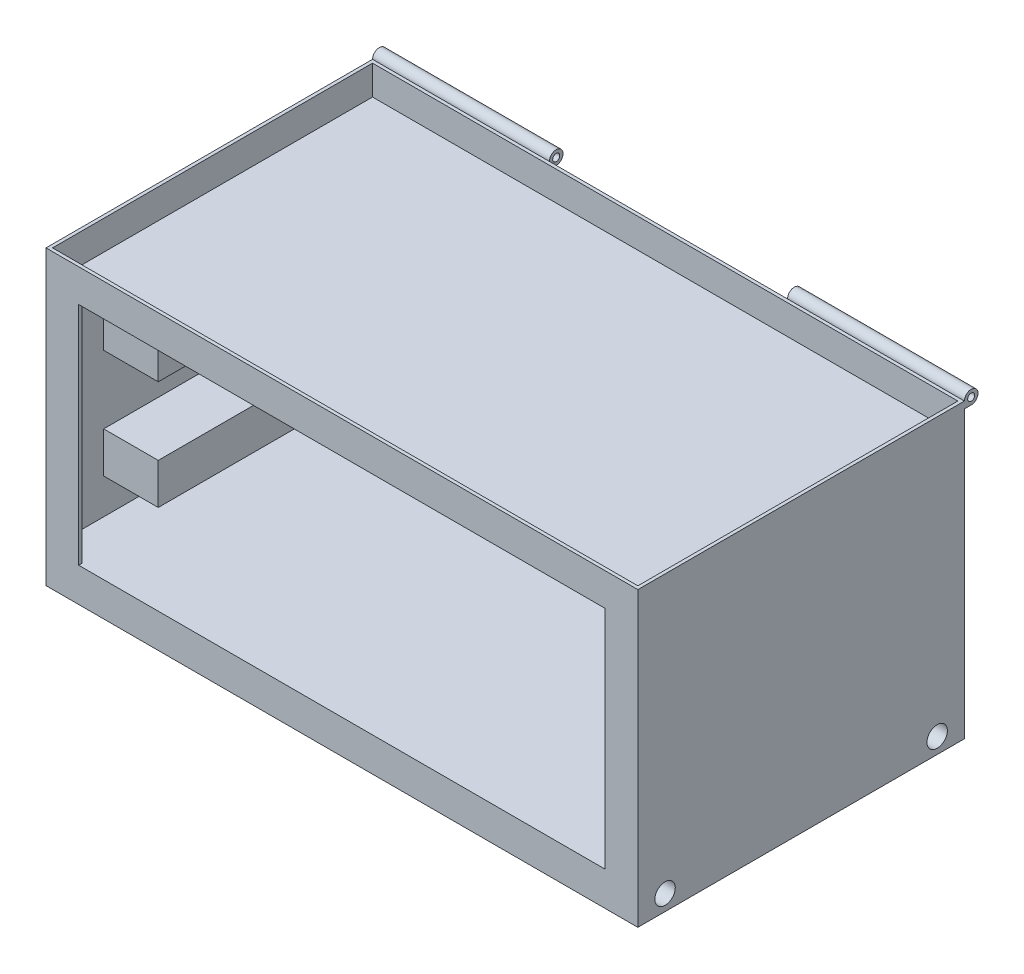
SolidWorks part; units mm, degrees
note: The reader was unsure of these and kept them because the rebuilt part matched: shared geometry of "Sketch1<13>", "Sketch1<14>", "Sketch1<15>".
material "AISI 4130 Steel, normalized at 870C"
ref_plane "Front Plane" through (0, 0, 0) normal (0, 0, 1) x (1, 0, 0)
ref_plane "Top Plane" through (0, 0, 0) normal (0, 1, 0) x (1, 0, 0)
ref_plane "Right Plane" through (0, 0, 0) normal (1, 0, 0) x (0, 0, -1)
sketch "Sketch1" plane through (0, 0, 0) normal (0, 1, 0) x (1, 0, 0)
  line L0 (0, 0) -> (-1.524, 0) construction
  line L9 (0, 0) -> (273.177, 0)
  line L10 (0, 0) -> (0, 149.352)
  line L11 (0, 149.352) -> (273.177, 149.352)
  line L12 (273.177, 0) -> (273.177, 149.352)
  line L13 (-1.524, -1.524) -> (274.701, -1.524)
  line L14 (-1.524, -1.524) -> (-1.524, 150.876)
  line L15 (-1.524, 150.876) -> (274.701, 150.876)
  line L16 (274.701, -1.524) -> (274.701, 150.876)
  line L17 (0, 149.352) -> (0, 150.876) construction
  line L18 (273.177, 149.352) -> (274.701, 149.352) construction
  line L19 (273.177, 0) -> (273.177, -1.524) construction
  line L20 (13.716, 0) -> (13.716, -1.524)
  line L21 (136.5885, 150.876) -> (136.5885, -1.524) construction
  line L22 (259.461, 0) -> (259.461, -1.524)
  dimension "D1" = 1.524
  dimension "D2" = 276.225
  dimension "D3" = 152.4
  dimension "D4" = 15.24
extrude "Bulk-Extrude" add sketch "Sketch1" against normal blind 136.525 contours L14 L13 L16 L15
extrude "Inner Shell-Cut" cut sketch "Sketch1<13>" against normal offset from surface (120.65 mm away) 15.875 contours L9 L12 L11 L10 | L22 L9 L20 L13 up to face at (136.5885, -136.525, -74.676)
sketch "Sketch1<13>" plane through (0, 0, 0) normal (0, 1, 0) x (1, 0, 0) same geometry as "Sketch1"
extrude "Top Wall-Extrude" add sketch "Sketch1<14>" against normal blind 15.24 contours L22 L9 L20 L13
sketch "Sketch1<14>" plane through (0, 0, 0) normal (0, 1, 0) x (1, 0, 0) same geometry as "Sketch1"
extrude "Top Floor-Extrude" add sketch "Sketch1<15>" along normal blind 1.524 from surface at -15.24 contours L9 L12 L11 L10 starting at face at (136.5885, -15.24, 0.762)
sketch "Sketch1<15>" plane through (0, 0, 0) normal (0, 1, 0) x (1, 0, 0) same geometry as "Sketch1"
ref_plane "Mid Plane" through (136.5885, 0, 0) normal (1, 0, 0) x (0, 0, -1)
sketch "Sketch5" plane through (274.701, 0, 0) normal (1, 0, 0) x (0, 0, -1)
  line L0 (150.876, 0) -> (154.051, 0)
  line L2 (154.051, -3.175) -> (150.876, -3.175)
  line L3 (150.876, -136.525) -> (150.876, 0) construction
  circle A0 centre (154.051, 0) radius 3.175
  circle A1 centre (154.051, 0) radius 1.651
  dimension "D1" = 1.524
  dimension "D2" = 6.35
extrude "Hinge-Extrude" add sketch "Sketch5" against normal blind 82.55
mirror "Mirror1" about plane through (136.5885, 0, 0) normal (1, 0, 0) of "Hinge-Extrude"
sketch "Sketch7" plane through (0, 0, -149.352) normal (0, 0, 1) x (1, 0, 0)
  line L0 (273.177, -120.65) -> (273.177, -15.24) construction
  line L1 (0, -34.29) -> (25.4635, -34.29)
  line L2 (0, -34.29) -> (0, -53.34)
  line L3 (0, -53.34) -> (25.4635, -53.34)
  line L4 (25.4635, -34.29) -> (25.4635, -53.34)
  line L5 (273.177, -34.29) -> (247.7135, -34.29)
  line L6 (273.177, -34.29) -> (273.177, -53.34)
  line L7 (273.177, -53.34) -> (247.7135, -53.34)
  line L8 (247.7135, -34.29) -> (247.7135, -53.34)
  line L9 (0, -120.65) -> (0, -15.24) construction
  line L10 (0, -85.09) -> (25.4635, -85.09)
  line L11 (0, -85.09) -> (0, -104.14)
  line L12 (0, -104.14) -> (25.4635, -104.14)
  line L13 (25.4635, -85.09) -> (25.4635, -104.14)
  line L14 (0, -15.24) -> (0, -34.29) construction
  line L15 (273.177, -85.09) -> (247.7135, -85.09)
  line L16 (273.177, -85.09) -> (273.177, -104.14)
  line L17 (273.177, -104.14) -> (247.7135, -104.14)
  line L18 (247.7135, -85.09) -> (247.7135, -104.14)
  line L19 (0, -15.24) -> (273.177, -15.24) construction
  line L20 (273.177, -15.24) -> (273.177, -34.29) construction
  line L21 (0, -53.34) -> (0, -85.09) construction
  line L22 (273.177, -53.34) -> (273.177, -85.09) construction
  dimension "D1" = 19.05
  dimension "D2" = 31.75
  dimension "D3" = 19.05
  dimension "D4" = 222.25
extrude "Rails-Extrude" add sketch "Sketch7" along normal offset from surface (125.476 mm away) 25.4 up to face at (136.5885, -68.2625, 1.524)
sketch "Sketch8" plane through (274.701, 0, 0) normal (1, 0, 0) x (0, 0, -1)
  line L0 (-1.524, -129.2098) -> (150.876, -129.2098) construction
  line L1 (-1.524, -136.525) -> (-1.524, 0) construction
  line L2 (150.876, -136.525) -> (150.876, -3.175) construction
  line L3 (-1.524, -136.525) -> (150.876, -136.525) construction
  line L4 (-1.524, -121.8946) -> (150.876, -121.8946) construction
  line L5 (-1.524, -135.89) -> (150.876, -135.89) construction
  line L6 (-0.889, -121.8946) -> (-0.889, -136.525) construction
  line L7 (150.241, -121.8946) -> (150.241, -136.525) construction
  line L8 (74.676, -135.89) -> (74.676, 0) construction
  line L9 (-1.524, 0) -> (150.876, 0) construction
  circle A0 centre (11.176, -129.2098) radius 4.7625
  circle A1 centre (138.176, -129.2098) radius 4.7625
  dimension "D6" = 9.525
  dimension "D7" = 12.7
  dimension "D1" = 7.3152
  dimension "D2" = 14.6304
  dimension "D3" = 0.635
  dimension "D4" = 0.635
  dimension "D5" = 0.635
extrude "Cut-Extrude1" cut sketch "Sketch8" against normal through all and the other way through all from surface at 0 starting at face at (274.701, -45.9279, -101.2439)
